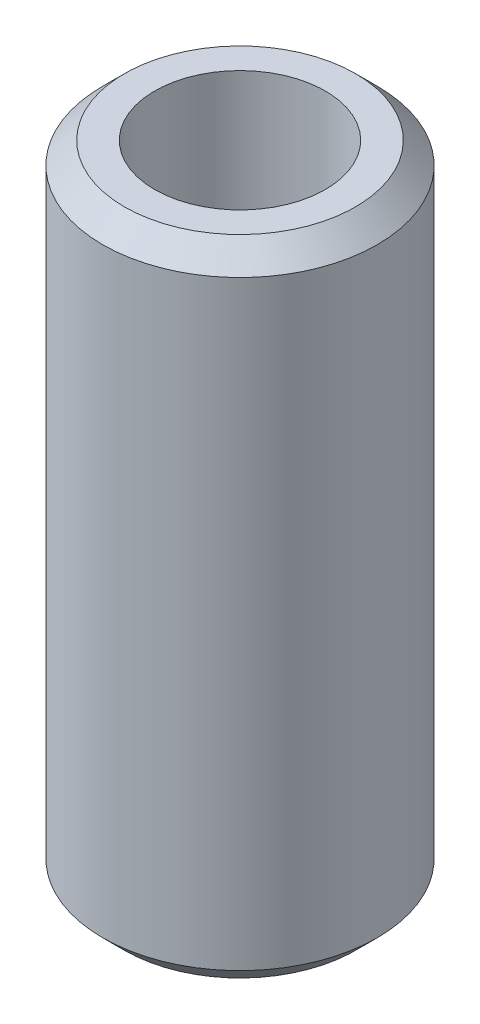
SolidWorks part; units mm, degrees
ref_plane "Front Plane" through (0, 0, 0) normal (0, 0, 1) x (1, 0, 0)
ref_plane "Top Plane" through (0, 0, 0) normal (0, 1, 0) x (1, 0, 0)
ref_plane "Right Plane" through (0, 0, 0) normal (1, 0, 0) x (0, 0, -1)
sketch "Sketch1" plane through (0, 0, 0) normal (0, 1, 0) x (1, 0, 0)
  circle A0 centre (0, 0) radius 17.5
  dimension "SHAFT_OD" = 35
extrude "Boss-Extrude1" add sketch "Sketch1" along normal blind 82.0724
sketch "Sketch2" plane through (0, 0, 0) normal (0, 1, 0) x (1, 0, 0)
  circle A0 centre (0, 0) radius 10.8823
  dimension "BORE_D" = 21.7647
extrude "Cut-Extrude1" cut sketch "Sketch2" along normal through all
chamfer "Chamfer1" distance 2.7794 angle 45 2 edges at (0, 82.0724, 17.5) (0, 0, 17.5)
